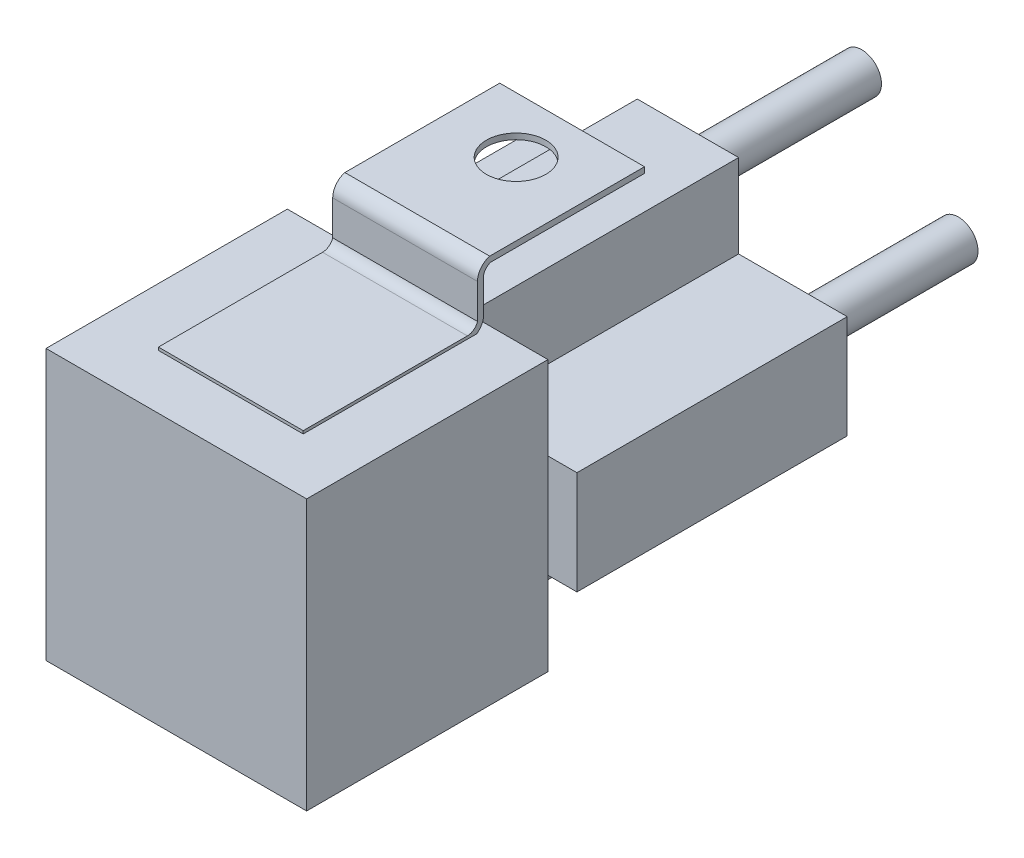
SolidWorks part; units mm, degrees
ref_plane "Front" through (0, 0, 0) normal (0, 0, 1) x (1, 0, 0)
ref_plane "Top" through (0, 0, 0) normal (0, 1, 0) x (1, 0, 0)
ref_plane "Right" through (0, 0, 0) normal (1, 0, 0) x (0, 0, -1)
sketch "Sketch1" plane through (0, 0, 0) normal (0, 0, 1) x (1, 0, 0)
  line L1 (-13.5, 14) -> (13.5, 14)
  line L2 (-13.5, 14) -> (-13.5, -14)
  line L3 (-13.5, -14) -> (13.5, -14)
  line L4 (13.5, 14) -> (13.5, -14)
  line L5 (-13.5, 14) -> (13.5, -14) construction
  line L6 (-13.5, -14) -> (13.5, 14) construction
  point P0 (0, 0)
  dimension "D1" = 27
  dimension "D2" = 28
extrude "Boss-Extrude1" add sketch "Sketch1" along normal blind 25
sketch "Sketch2" plane through (0, 0, 0) normal (0, 0, 1) x (1, 0, 0)
  line L0 (13.5, 14) -> (-13.5, 14) construction
  line L1 (-16.5, -5.35) -> (16.5, -5.35)
  line L2 (-16.5, -5.35) -> (-16.5, 5.35)
  line L3 (-16.5, 5.35) -> (16.5, 5.35)
  line L4 (16.5, -5.35) -> (16.5, 5.35)
  line L5 (-16.5, -5.35) -> (16.5, 5.35) construction
  line L6 (-16.5, 5.35) -> (16.5, -5.35) construction
  line L7 (-5.25, -14) -> (5.25, -14)
  line L8 (-5.25, -14) -> (-5.25, 14)
  line L9 (-5.25, 14) -> (5.25, 14)
  line L10 (5.25, -14) -> (5.25, 14)
  line L11 (-5.25, -14) -> (5.25, 14) construction
  line L12 (-5.25, 14) -> (5.25, -14) construction
  point P0 (0, 0)
  point P5 (0, 0)
  dimension "D1" = 10.7
  dimension "D2" = 33
  dimension "D3" = 10.5
extrude "Boss-Extrude2" add sketch "Sketch2" against normal blind 28 contours L3 L4 L1 L2 | L8 L9 L10 L7
sketch "Sketch3" plane through (0, 0, -28) normal (0, 0, -1) x (-1, 0, 0)
  line L0 (0, 10) -> (0, 0) construction
  line L1 (0, 0) -> (0, -10) construction
  line L2 (-10, 0) -> (0, 0) construction
  line L3 (0, 0) -> (10, 0) construction
  circle A0 centre (-10, 0) radius 2.05
  circle A1 centre (10, 0) radius 2.05
  circle A2 centre (0, 10) radius 2.05
  circle A3 centre (0, -10) radius 2.05
  dimension "D1" = 4.1
  dimension "D2" = 10
extrude "Boss-Extrude3" add sketch "Sketch3" along normal blind 18
sketch "Sketch4" plane through (0, 0, 0) normal (1, 0, 0) x (0, 0, -1)
  line L0 (-19.3565, 14) -> (-2.3491, 14)
  line L1 (-25, 14) -> (0, 14) construction
  line L2 (-1, 15.0261) -> (-1, 18.6584)
  line L3 (0, 20) -> (16, 20)
  line L5 (28, 14) -> (0, 14) construction
  arc A0 (-2.3491, 14) -> (-1, 15.0261) centre (-2.3491, 15.4) ccw
  arc A1 (-1, 18.6584) -> (0, 20) centre (0.4, 18.6584) cw
  dimension "D1" = 6
  dimension "D4" = 1.4
  dimension "D2" = 16
  dimension "D3" = 1
extrude "Extrude-Thin1" add sketch "Sketch4" along normal mid plane 15 thin thin type mid plane wall 0.6
sketch "Sketch5" plane through (0, 20.3, 0) normal (0, 1, 0) x (1, 0, 0)
  circle A0 centre (0, 10.2) radius 3.075
  dimension "D1" = 6.15
  dimension "D2" = 10.2
extrude "Mounting Hole" cut sketch "Sketch5" against normal up to next
